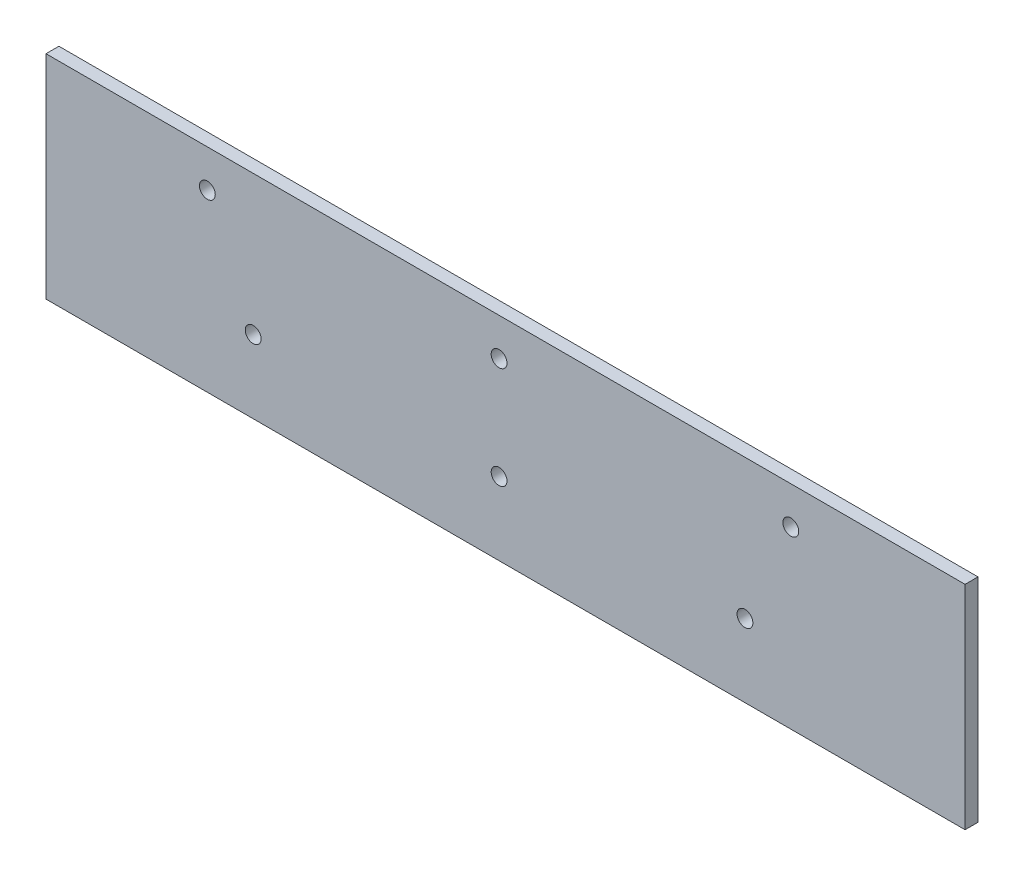
SolidWorks part; units mm, degrees
ref_plane "Front Plane" through (0, 0, 0) normal (0, 0, 1) x (1, 0, 0)
ref_plane "Top Plane" through (0, 0, 0) normal (0, 1, 0) x (1, 0, 0)
ref_plane "Right Plane" through (0, 0, 0) normal (1, 0, 0) x (0, 0, -1)
sketch "Sketch1" plane through (0, 0, 0) normal (0, 0, 1) x (1, 0, 0)
  line L1 (-110.2662, -25.5) -> (110.2662, -25.5)
  line L2 (-110.2662, -25.5) -> (-110.2662, 25.5)
  line L3 (-110.2662, 25.5) -> (110.2662, 25.5)
  line L4 (110.2662, -25.5) -> (110.2662, 25.5)
  line L5 (-110.2662, -25.5) -> (110.2662, 25.5) construction
  line L6 (-110.2662, 25.5) -> (110.2662, -25.5) construction
  point P0 (0, 0)
  dimension "D1" = 51
  dimension "D2" = 220.5325
extrude "Boss-Extrude1" add sketch "Sketch1" along normal blind 3.1
sketch "Sketch2" plane through (0, 0, 3.1) normal (0, 0, 1) x (1, 0, 0)
  point P0 (-71.55, 16.5)
  point P1 (-1.55, 16.5)
  point P3 (68.45, 16.5)
  point P5 (-1.55, -8)
  point P7 (57.45, -8)
  point P9 (-60.55, -8)
hole_wizard "#6 Clearance Hole1" positions "Sketch3" profile "Sketch4" hole size "#6" standard "ANSI Inch" end condition through all
sketch "Sketch3" plane through (0, 0, 3.1) normal (0, 0, 1) x (1, 0, 0)
  point P0 (-71.55, 16.5)
  point P3 (-60.55, -8)
  point P6 (-1.55, -8)
  point P9 (-1.55, 16.5)
  point P12 (68.45, 16.5)
  point P15 (57.45, -8)
sketch "Sketch4" plane through (-71.55, 16.5, 3.1) normal (1, 0, 0) x (0, -1, 0)
  line L0 (0, 0) -> (0, 3.1)
  line L1 (0, 3.1) -> (1.8986, 3.1)
  line L2 (1.8986, 3.1) -> (1.8986, 0)
  line L5 (1.8986, 0) -> (0, 0)
  line L11 (0, -6.35) -> (0, 107.95) construction
  dimension "Thru Hole Dia." = 3.7973
  dimension "Thru Hole Depth" = 3.1
